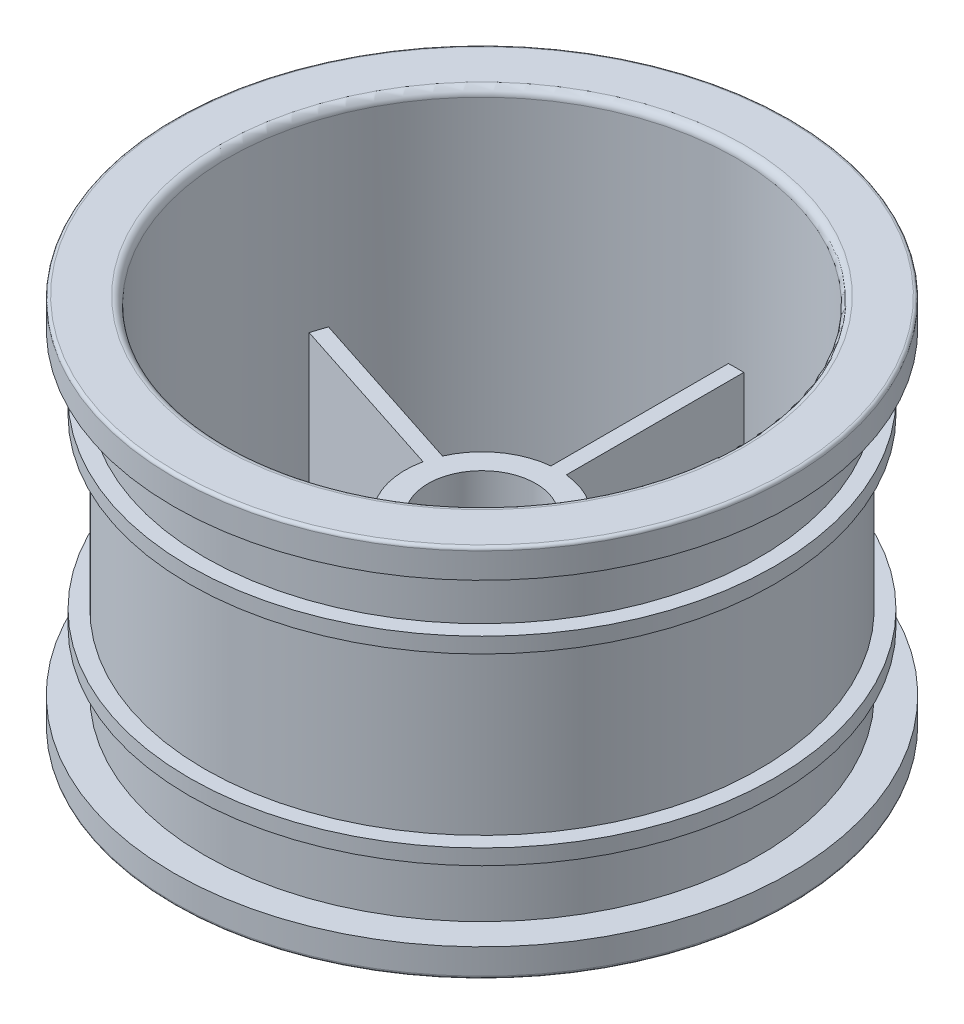
SolidWorks part; units mm, degrees
ref_plane "前视基准面" through (0, 0, 0) normal (0, 0, 1) x (1, 0, 0)
ref_plane "上视基准面" through (0, 0, 0) normal (0, 1, 0) x (1, 0, 0)
ref_plane "右视基准面" through (0, 0, 0) normal (1, 0, 0) x (0, 0, -1)
sketch "草图1" plane through (0, 0, 0) normal (0, 0, 1) x (1, 0, 0)
  line L0 (0, 0) -> (0, 24.3) construction
  line L1 (-20, 24.1) -> (-20, 22.45)
  line L2 (-20, 22.45) -> (-18, 22.45)
  line L3 (-18, 22.45) -> (-18, 18.6)
  line L4 (-18, 18.6) -> (-19, 18.6)
  line L5 (-19, 18.6) -> (-19, 17.6)
  line L6 (-19, 17.6) -> (-18, 17.6)
  line L7 (-18, 17.6) -> (-18, 6.7)
  line L8 (0, 12.15) -> (-28.3099, 12.15) construction
  line L9 (-19.8, 24.3) -> (-17, 24.3)
  line L10 (-16.5, 23.8) -> (-16.5, 0.5)
  line L11 (-19.8, 0) -> (-17, 0)
  line L12 (-19, 6.7) -> (-18, 6.7)
  line L13 (-19, 5.7) -> (-19, 6.7)
  line L14 (-18, 5.7) -> (-19, 5.7)
  line L15 (-18, 1.85) -> (-18, 5.7)
  line L16 (-20, 1.85) -> (-18, 1.85)
  line L17 (-20, 0.2) -> (-20, 1.85)
  arc A0 (-17, 24.3) -> (-16.5, 23.8) centre (-17, 23.8) cw
  arc A1 (-17, 0) -> (-16.5, 0.5) centre (-17, 0.5) ccw
  arc A2 (-19.8, 0) -> (-20, 0.2) centre (-19.8, 0.2) cw
  arc A3 (-20, 24.1) -> (-19.8, 24.3) centre (-19.8, 24.1) cw
  point P20 (-16.5, 12.15)
  point P22 (-18, 12.15)
  point P29 (-20, 0)
  point P32 (-20, 24.3)
  dimension "D9" = 0.5
  dimension "D10" = 0.2
  dimension "D1" = 24.3
  dimension "D2" = 1.85
  dimension "D3" = 3.85
  dimension "D4" = 1
  dimension "D5" = 1
  dimension "D6" = 20
  dimension "D7" = 18
  dimension "D8" = 3.5
revolve "旋转1" add sketch "草图1" angle 360 about L0
ref_plane "基准面1" through (0, 0, -24) normal (0, 0, 1) x (1, 0, 0)
sketch "草图9" plane through (0, 0, 0) normal (1, 0, 0) x (0, 0, -1)
  line L0 (0, 0) -> (0, 12) construction
  line L1 (-12.0811, 9.4816) -> (-12.0811, -1.2) construction
  line L2 (-16.5, 0.5) -> (-16.5, 2.5)
  line L3 (-3.5, 1.8) -> (-3.5, 12) construction
  line L4 (-3.5, 12) -> (-5, 12)
  line L5 (-5, 12) -> (-5, 4)
  line L6 (-3.5, 1.8) -> (-2, 1.8)
  line L7 (-2, 1.8) -> (-2, 12)
  line L8 (-2, 12) -> (-3.5, 12)
  arc A0 (-17, 0) -> (-6.5, 0.374) centre (-12.0811, 9.4816) ccw
  arc A1 (-6.5, 0.374) -> (-3.5, 1.8) centre (1.6975, -13.0032) cw
  arc A2 (-17, 0) -> (-16.5, 0.5) centre (-17, 0.5) ccw
  arc A3 (-16.5, 2.5) -> (-5, 4) centre (-16.9234, 50.5796) ccw
  dimension "D6" = 0.5
  dimension "D10" = 10.6816
  dimension "D11" = 48.0815
  dimension "D1" = 12
  dimension "D2" = 6.5
  dimension "D3" = 2
  dimension "D4" = 3
  dimension "D5" = 1.2
  dimension "D7" = 2.5
  dimension "D8" = 1.5
  dimension "D9" = 8
revolve "旋转3" add sketch "草图9" angle 360 about L0
ref_plane "基准面2" through (0, -5, 0) normal (0, 1, 0) x (1, 0, 0)
sketch "草图10" plane through (0, -5, 0) normal (0, 1, 0) x (1, 0, 0)
  line L0 (0, 2.0432) -> (0, -25.755) construction
  line L1 (0, -16.5) -> (-15.3557, -16.5) construction
  line L2 (0, -8) -> (-3.2103, -8) construction
  arc A0 (1.5614, -8.6264) -> (-1.5614, -8.6264) centre (0, -10.2593) ccw
  arc A1 (-6.5628, -15.1387) -> (6.5628, -15.1387) centre (0, 0) ccw
  arc A2 (1.5614, -8.6264) -> (6.7, -14.6688) centre (-25.0914, -36.4986) cw
  arc A3 (6.7, -14.6688) -> (6.5628, -15.1387) centre (6.4362, -14.8468) cw
  arc A4 (-6.7, -14.6688) -> (-6.5628, -15.1387) centre (-6.4362, -14.8468) ccw
  arc A5 (-1.5614, -8.6264) -> (-6.7, -14.6688) centre (25.0914, -36.4986) ccw
  dimension "D4" = 33
  dimension "D1" = 8.5
  dimension "D2" = 6.7
extrude "切除-拉伸3" cut sketch "草图10" along normal up to surface (8.1951 mm away) up to face at (0, 2.5, 16.5)
ref_axis "基准轴1" through (0, 0, 0) along (0, 1, 0)
sketch "草图12" plane through (0, 0, 0) normal (0, 1, 0) x (1, 0, 0)
  line L0 (-9.3667, 0) -> (10.1437, 0) construction
ref_plane "基准面4" through (0, 0, 0) normal (0, 0.0698, 0.9976) x (1, 0, 0)
pattern_circular "阵列(圆周)2" count 5 every 72 about axis through (0, 0, 0) along (0, 1, 0) of "切除-拉伸3"
sketch "草图11" plane through (0, 0, 0) normal (0, 0, 1) x (1, 0, 0)
  line L0 (0, 0) -> (0, -1.2) construction
  circle A0 centre (0, -1.2) radius 1.75
  dimension "D2" = 3.5
  dimension "D1" = 1.2
extrude "切除-拉伸4" cut sketch "草图11" along direction (0, 0.0698, 0.9976) on the side against the normal through all
pattern_circular "阵列(圆周)3" count 5 every 72 about axis through (0, 0, 0) along (0, 1, 0) of "切除-拉伸4"
sketch "草图13" plane through (0, 12, 0) normal (0, 1, 0) x (1, 0, 0)
  line L0 (0, 0) -> (9.6985, -13.3488) construction
  line L1 (10.0985, -13.0488) -> (3.3287, -3.7309)
  line L2 (9.2895, -13.6365) -> (2.5197, -4.3187)
  arc A0 (6.5628, -15.1387) -> (12.3697, -10.9197) centre (0, 0) ccw construction
  arc A1 (6.5628, -15.1387) -> (12.3697, -10.9197) centre (0, 0) ccw construction
  circle A2 centre (0, 0) radius 5 construction
  arc A3 (2.5197, -4.3187) -> (3.3287, -3.7309) centre (0, 0) ccw
  arc A4 (6.5628, -15.1387) -> (12.3697, -10.9197) centre (0, 0) ccw construction
  arc A5 (10.0985, -13.0488) -> (9.2895, -13.6365) centre (0, 0) cw
  dimension "D1" = 0.5
extrude "凸台-拉伸1" add sketch "草图13" against normal up to next
pattern_circular "阵列(圆周)4" count 5 every 72 about axis through (0, 0, 0) along (0, 1, 0) of "凸台-拉伸1"
sketch "草图14" plane through (0, 1.8, 0) normal (0, -1, 0) x (1, 0, 0)
  circle A2 centre (0, 0) radius 3.5
  dimension "D1" = 7
extrude "切除-拉伸5" cut sketch "草图14" against normal blind 2
sketch "草图15" plane through (0, 12, 0) normal (0, 1, 0) x (1, 0, 0)
  circle A0 centre (0, 0) radius 3.5
  dimension "D1" = 7
extrude "切除-拉伸6" cut sketch "草图15" against normal blind 2.2
sketch "草图16" plane through (0, 0, 0) normal (1, 0, 0) x (0, 0, -1)
  line L0 (0, 619.0795) -> (0, -679.4818)
